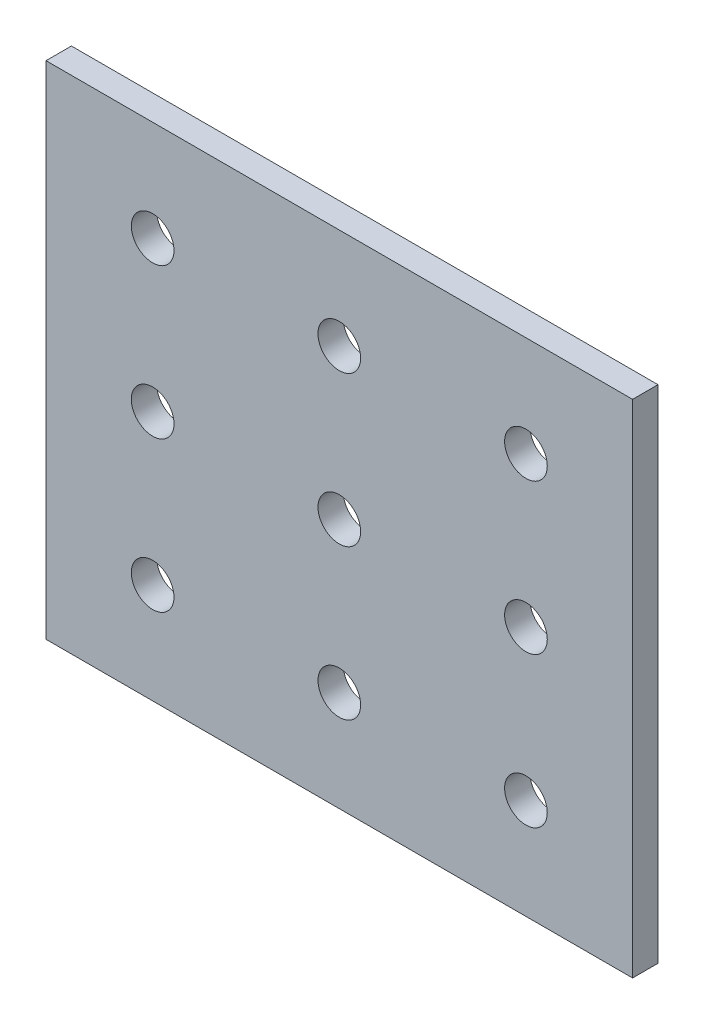
SolidWorks part; units mm, degrees
ref_plane "Alzado" through (0, 0, 0) normal (0, 0, 1) x (1, 0, 0)
ref_plane "Planta" through (0, 0, 0) normal (0, 1, 0) x (1, 0, 0)
ref_plane "Vista lateral" through (0, 0, 0) normal (1, 0, 0) x (0, 0, -1)
sketch "Croquis1" plane through (0, 0, 0) normal (0, 0, 1) x (1, 0, 0)
  line L1 (0, 0) -> (90, 0)
  line L2 (0, 0) -> (0, 76.2)
  line L3 (0, 76.2) -> (90, 76.2)
  line L4 (90, 0) -> (90, 76.2)
  circle A0 centre (45, 38.1) radius 4
  circle A1 centre (10, 9.95) radius 4
  circle A2 centre (10, 66.25) radius 4
  circle A3 centre (80, 66.25) radius 4
  circle A4 centre (80, 9.95) radius 4
  circle A5 centre (45, 66.25) radius 4
  circle A6 centre (10, 38.1) radius 4
  circle A7 centre (80, 38.1) radius 4
  circle A8 centre (45, 9.95) radius 4
  dimension "D3" = 8
  dimension "D5" = 8
  dimension "D7" = 8
  dimension "D10" = 8
  dimension "D11" = 8
  dimension "D12" = 8
  dimension "D13" = 8
  dimension "D14" = 8
  dimension "D15" = 8
  dimension "D1" = 76.2
  dimension "D2" = 90
  dimension "D4" = 10
  dimension "D6" = 9.95
  dimension "D8" = 9.95
  dimension "D9" = 10
extrude "Saliente-Extruir1" add sketch "Croquis1" along normal blind 0.4763
sketch "Croquis2" plane through (0, 0, 0.4763) normal (0, 0, 1) x (1, 0, 0)
extrude "Saliente-Extruir2" add sketch "Croquis1<2>" along normal blind 4.7625
sketch "Croquis1<2>" plane through (0, 0, 0) normal (0, 0, 1) x (1, 0, 0) same geometry as "Croquis1"
sketch "Croquis3" plane through (0, 0, 0) normal (0, -1, 0) x (1, 0, 0)
  line L1 (90, 4.7625) -> (0, 4.7625)
  line L2 (90, 4.7625) -> (90, 0)
  line L3 (90, 0) -> (0, 0)
  line L4 (0, 4.7625) -> (0, 0)
extrude "Saliente-Extruir3" add sketch "Croquis3" along normal blind 4.445
sketch "Croquis5" plane through (0, 76.2, 0) normal (0, 1, 0) x (1, 0, 0)
  line L1 (90, -4.7625) -> (0, -4.7625)
  line L2 (90, -4.7625) -> (90, 0)
  line L3 (90, 0) -> (0, 0)
  line L4 (0, -4.7625) -> (0, 0)
extrude "Saliente-Extruir4" add sketch "Croquis5" along normal blind 4.445
sketch "Croquis6" plane through (0, 0, 0) normal (-1, 0, 0) x (0, 0, 1)
  line L1 (0, -4.445) -> (4.7625, -4.445)
  line L2 (0, -4.445) -> (0, 80.645)
  line L3 (0, 80.645) -> (4.7625, 80.645)
  line L4 (4.7625, -4.445) -> (4.7625, 80.645)
extrude "Saliente-Extruir5" add sketch "Croquis6" along normal blind 5
sketch "Croquis7" plane through (90, 0, 0) normal (1, 0, 0) x (0, 0, -1)
  line L1 (0, -4.445) -> (-4.7625, -4.445)
  line L2 (0, -4.445) -> (0, 80.645)
  line L3 (0, 80.645) -> (-4.7625, 80.645)
  line L4 (-4.7625, -4.445) -> (-4.7625, 80.645)
extrude "Saliente-Extruir6" add sketch "Croquis7" along normal blind 5
sketch "Croquis8" plane through (0, -4.445, 0) normal (0, -1, 0) x (1, 0, 0)
  line L1 (95, 0) -> (-5, 0)
  line L2 (95, 0) -> (95, 4.7625)
  line L3 (95, 4.7625) -> (-5, 4.7625)
  line L4 (-5, 0) -> (-5, 4.7625)
extrude "Saliente-Extruir7" add sketch "Croquis8" along normal blind 4.445
sketch "Croquis9" plane through (0, 80.645, 0) normal (0, 1, 0) x (1, 0, 0)
  line L1 (95, 0) -> (-5, 0)
  line L2 (95, 0) -> (95, -4.7625)
  line L3 (95, -4.7625) -> (-5, -4.7625)
  line L4 (-5, 0) -> (-5, -4.7625)
extrude "Saliente-Extruir8" add sketch "Croquis9" along normal blind 4.445
sketch "Croquis10" plane through (95, 0, 0) normal (1, 0, 0) x (0, 0, -1)
  line L1 (0, -8.89) -> (-4.7625, -8.89)
  line L2 (0, -8.89) -> (0, 85.09)
  line L3 (0, 85.09) -> (-4.7625, 85.09)
  line L4 (-4.7625, -8.89) -> (-4.7625, 85.09)
extrude "Saliente-Extruir9" add sketch "Croquis10" along normal blind 5
sketch "Croquis12" plane through (-5, 0, 0) normal (-1, 0, 0) x (0, 0, 1)
  line L1 (0, -8.89) -> (4.7625, -8.89)
  line L2 (0, -8.89) -> (0, 85.09)
  line L3 (0, 85.09) -> (4.7625, 85.09)
  line L4 (4.7625, -8.89) -> (4.7625, 85.09)
extrude "Saliente-Extruir10" add sketch "Croquis12" along normal blind 5
